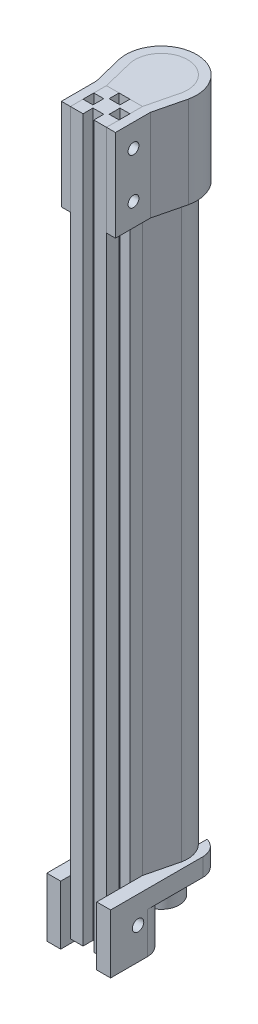
SolidWorks part; units mm, degrees
material "A286 Iron Base Superalloy"
ref_plane "Front Plane" through (0, 0, 0) normal (0, 0, 1) x (1, 0, 0)
ref_plane "Top Plane" through (0, 0, 0) normal (0, 1, 0) x (1, 0, 0)
ref_plane "Right Plane" through (0, 0, 0) normal (1, 0, 0) x (0, 0, -1)
sketch "Sketch1" plane through (0, 0, 0) normal (0, 1, 0) x (1, 0, 0)
  line L0 (14.2987, -2.9258) -> (10, -20.405)
  line L1 (10, -20.405) -> (-10, -20.405)
  line L2 (-10, -20.405) -> (-14.2987, -2.9258)
  line L3 (0, 14.595) -> (-46.807, 14.595) construction
  arc A0 (14.2987, -2.9258) -> (-14.2987, -2.9258) centre (0, 0) ccw
  point P10 (0, -20.405)
  dimension "D1" = 29.19
  dimension "D2" = 18
  dimension "D3" = 35
  dimension "D4" = 20
extrude "Boss-Extrude1" add sketch "Sketch1" along normal blind 369.57
sketch "Sketch2" plane through (0, 369.57, 0) normal (0, 1, 0) x (1, 0, 0)
  line L0 (-10, -20.405) -> (10, -20.405) construction
  line L1 (-10, -20.405) -> (10, -20.405)
  line L2 (-10, -20.405) -> (-10, -40.405)
  line L3 (-10, -40.405) -> (10, -40.405)
  line L4 (10, -20.405) -> (10, -40.405)
  point P8 (0, -20.405)
  point P9 (0, -20.405)
  dimension "D1" = 20
extrude "Boss-Extrude2" add sketch "Sketch2" against normal blind 400 separate body
sketch "Sketch7" plane through (0, 369.57, 0) normal (0, 1, 0) x (1, 0, 0)
  line L0 (10, -40.405) -> (10, -20.405) construction
  line L1 (10, -27.405) -> (4.5, -27.405)
  line L2 (10, -27.405) -> (10, -33.405)
  line L3 (10, -33.405) -> (4.5, -33.405)
  line L4 (4.5, -27.405) -> (4.5, -33.405)
  line L5 (0, -40.405) -> (0, 0) construction
  line L6 (-10, -40.405) -> (10, -40.405) construction
  line L7 (-10, -27.405) -> (-10, -33.405)
  line L8 (-10, -33.405) -> (-4.5, -33.405)
  line L9 (-4.5, -27.405) -> (-4.5, -33.405)
  line L10 (-10, -27.405) -> (-4.5, -27.405)
  line L11 (-10, -20.405) -> (10, -20.405) construction
  line L12 (-3, -20.405) -> (3, -20.405)
  line L13 (-3, -20.405) -> (-3, -25.905)
  line L14 (-3, -25.905) -> (3, -25.905)
  line L15 (3, -20.405) -> (3, -25.905)
  line L16 (-10, -30.405) -> (10, -30.405) construction
  line L17 (-3, -34.905) -> (3, -34.905)
  line L18 (3, -40.405) -> (3, -34.905)
  line L19 (-3, -40.405) -> (3, -40.405)
  line L20 (-3, -40.405) -> (-3, -34.905)
  point P12 (10, -30.405)
  point P13 (10, -30.405)
  point P25 (0, -20.405)
  dimension "D1" = 6
  dimension "D2" = 5.5
  dimension "D3" = 5.5
  dimension "D4" = 6
extrude "Cut-Extrude3" cut sketch "Sketch7" against normal through all
sketch "Sketch8" plane through (0, 369.57, 0) normal (0, 1, 0) x (1, 0, 0)
  line L0 (-10, -40.405) -> (-10, -20.405)
  line L1 (-10, -33.405) -> (-10, -40.405) construction
  line L2 (-14.2987, -2.9258) -> (-10, -20.405) construction
  line L3 (-10, -20.405) -> (-14.2987, -2.9258)
  line L4 (14.2987, -2.9258) -> (10, -20.405)
  line L5 (10, -20.405) -> (14.2987, -2.9258) construction
  line L6 (10, -20.405) -> (10, -40.405)
  line L7 (10, -40.405) -> (10, -33.405) construction
  line L8 (-15, -40.405) -> (-15, -21.0108)
  line L9 (-15, -21.0108) -> (-19.1758, -4.0315)
  line L10 (19.1758, -4.0315) -> (15, -21.0108)
  line L11 (15, -21.0108) -> (15, -40.405)
  line L12 (-15, -40.405) -> (-10, -40.405)
  line L13 (10, -40.405) -> (15, -40.405)
  line L14 (-10, -33.405) -> (-4.5, -33.405) construction
  arc A0 (-14.2987, -2.9258) -> (14.2987, -2.9258) centre (0, 0) cw
  arc A1 (14.2987, -2.9258) -> (-14.2987, -2.9258) centre (0, 0) ccw construction
  arc A2 (-19.1758, -4.0315) -> (19.1758, -4.0315) centre (0, 0) cw
  dimension "D1" = 5
  dimension "D2" = 7
extrude "Boss-Extrude3" add sketch "Sketch8" against normal blind 50.8 separate body
sketch "Sketch9" plane through (-15, 0, 0) normal (-1, 0, 0) x (0, 0, 1)
  line L0 (40.405, 344.17) -> (-19.595, 344.17) construction
  line L1 (40.405, 318.77) -> (40.405, 369.57) construction
  line L2 (-19.595, 369.57) -> (-19.595, 318.77) construction
  line L3 (33.405, -30.43) -> (33.405, 369.57) construction
  line L5 (21.0108, 369.57) -> (40.405, 369.57) construction
  circle A0 centre (30.405, 356.87) radius 3
  circle A1 centre (30.405, 331.47) radius 3
  dimension "D1" = 6
  dimension "D2" = 12.7
extrude "Cut-Extrude4" cut sketch "Sketch9" against normal through all
sketch "Sketch10" plane through (0, 0, 0) normal (0, -1, 0) x (1, 0, 0)
  circle A0 centre (0, 0) radius 9.975
  dimension "D1" = 19.95
extrude "Boss-Extrude4" add sketch "Sketch10" along normal blind 24.4221
sketch "Sketch11" plane through (0, 0, 0) normal (0, -1, 0) x (1, 0, 0)
  line L0 (-10, 20.405) -> (10, 20.405) construction
  line L1 (-17.7, 10.405) -> (17.7, 10.405)
  line L2 (-17.7, 10.405) -> (-17.7, 20.405)
  line L3 (-17.7, 20.405) -> (17.7, 20.405)
  line L4 (17.7, 10.405) -> (17.7, 20.405)
  point P6 (0, 20.405)
  dimension "D1" = 10
  dimension "D2" = 35.4
extrude "Boss-Extrude5" add sketch "Sketch11" along normal blind 10 separate body
sketch "Sketch12" plane through (0, -10, 0) normal (0, -1, 0) x (1, 0, 0)
  line L1 (-17.7, 20.405) -> (17.7, 20.405)
  line L2 (-17.7, 20.405) -> (-17.7, 15.405)
  line L3 (-17.7, 15.405) -> (17.7, 15.405)
  line L4 (17.7, 20.405) -> (17.7, 15.405)
  line L5 (17.7, 10.405) -> (17.7, 20.405) construction
  dimension "D1" = 5
  dimension "D2" = 35.4
extrude "Boss-Extrude6" add sketch "Sketch12" along normal blind 22.7
sketch "Sketch14" plane through (0, 0, 15.405) normal (0, 0, -1) x (-1, 0, 0)
  line L0 (17.7, -10) -> (-17.7, -10) construction
  circle A0 centre (0, -15) radius 3.175
  dimension "D1" = 6.35
  dimension "D2" = 5
extrude "Cut-Extrude5" cut sketch "Sketch14" against normal through all
sketch "Sketch15" plane through (0, 0, 20.405) normal (0, 0, 1) x (1, 0, 0)
  line L0 (-10, -30.43) -> (-10, 369.57) construction
  line L1 (-17.7, 0) -> (-10, 0)
  line L2 (-17.7, 0) -> (-17.7, -32.7)
  line L3 (-17.7, -32.7) -> (-10, -32.7)
  line L4 (-10, 0) -> (-10, -32.7)
  line L5 (17.7, -32.7) -> (-17.7, -32.7) construction
  line L6 (10, -30.43) -> (10, 369.57) construction
  line L7 (10, 0) -> (17.7, 0)
  line L8 (10, 0) -> (10, -32.7)
  line L9 (10, -32.7) -> (17.7, -32.7)
  line L10 (17.7, 0) -> (17.7, -32.7)
  line L11 (17.7, 0) -> (-17.7, 0) construction
extrude "Boss-Extrude7" add sketch "Sketch15" along normal blind 25.4
sketch "Sketch16" plane through (17.7, 0, 0) normal (1, 0, 0) x (0, 0, -1)
  line L2 (-10.405, -10) -> (-15.405, -10) construction
  line L3 (-27.405, -30.43) -> (-27.405, 331.47) construction
  circle A0 centre (-30.58, -15) radius 3.175
  dimension "D1" = 6.35
  dimension "D2" = 5
extrude "Cut-Extrude6" cut sketch "Sketch16" against normal through all
sketch "Sketch17" plane through (0, 0, 10.405) normal (0, 0, -1) x (-1, 0, 0)
  line L1 (17.7, -10) -> (10.475, -10)
  line L2 (17.7, -10) -> (17.7, 0)
  line L3 (17.7, 0) -> (10.475, 0)
  line L4 (10.475, -10) -> (10.475, 0)
  line L5 (9.975, -24.4221) -> (9.975, 0) construction
  line L6 (0, -32.7) -> (0, 0) construction
  line L7 (17.7, -32.7) -> (-17.7, -32.7) construction
  line L8 (-17.7, 0) -> (-10.475, 0)
  line L9 (-10.475, -10) -> (-10.475, 0)
  line L10 (-17.7, -10) -> (-10.475, -10)
  line L11 (-17.7, -10) -> (-17.7, 0)
  line L12 (17.7, 0) -> (-17.7, 0) construction
  dimension "D1" = 0.5
extrude "Boss-Extrude8" add sketch "Sketch17" along normal blind 25.4
fillet "Fillet1" radius 10 4 edges at (17.7, -21.35, 15.405) (-17.7, -21.35, 15.405) (17.7, -5, -14.995) (-17.7, -5, -14.995)
